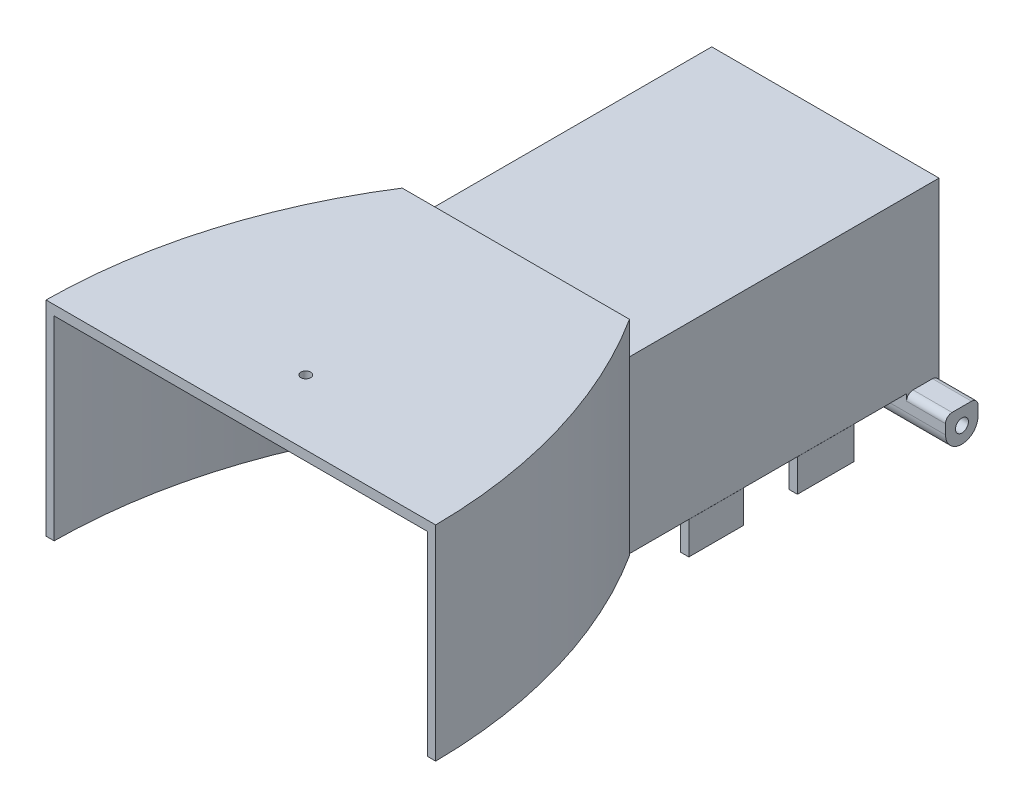
SolidWorks part; units mm, degrees
ref_plane "정면" through (0, 0, 0) normal (0, 0, 1) x (1, 0, 0)
ref_plane "윗면" through (0, 0, 0) normal (0, 1, 0) x (1, 0, 0)
ref_plane "우측면" through (0, 0, 0) normal (1, 0, 0) x (0, 0, -1)
sketch "스케치1" plane through (0, 0, 0) normal (0, 0, 1) x (1, 0, 0)
  line L1 (0, 0) -> (70, 0)
  line L2 (0, 0) -> (0, -70)
  line L3 (0, -70) -> (70, -70)
  line L4 (70, 0) -> (70, -70)
  dimension "D1" = 70
  dimension "D2" = 70
extrude "보스-돌출1" add sketch "스케치1" along normal blind 180 contours L1 L4 L3 L2
sketch "스케치3" plane through (0, 0, 180) normal (0, 0, 1) x (1, 0, 0)
  line L0 (0, 0) -> (70, 0) construction
  line L1 (2.5, -2.5) -> (67.5, -2.5)
  line L2 (2.5, -2.5) -> (2.5, -67.5)
  line L3 (2.5, -67.5) -> (67.5, -67.5)
  line L4 (67.5, -2.5) -> (67.5, -67.5)
  line L5 (70, 0) -> (70, -70) construction
  dimension "D1" = 65
  dimension "D2" = 65
  dimension "D3" = 2.5
  dimension "D4" = 2.5
extrude "컷-돌출1" cut sketch "스케치3" against normal blind 173 contours L1 L4 L3 L2
sketch "스케치4" plane through (0, 0, 0) normal (0, 0, -1) x (-1, 0, 0)
  line L0 (-35, 0) -> (-35, -51.7734)
  line L1 (0, 0) -> (-70, 0) construction
  line L2 (0, -70) -> (-70, -70) construction
  circle A0 centre (-35, -35) radius 10.95
  dimension "D1" = 21.9
  dimension "D2" = 35
extrude "컷-돌출2" cut sketch "스케치4" against normal blind 137 contours A0
sketch "스케치5" plane through (70, 0, 0) normal (1, 0, 0) x (0, 0, -1)
  line L0 (-180, 0) -> (-180, -70) construction
  line L1 (-180, -7.5) -> (-130, -7.5)
  line L2 (-180, -7.5) -> (-180, -62.5)
  line L3 (-180, -62.5) -> (-130, -62.5)
  line L4 (-130, -7.5) -> (-130, -62.5)
  line L5 (-180, 0) -> (0, 0) construction
  line L7 (-180, -70) -> (0, -70) construction
  dimension "D1" = 7.5
  dimension "D2" = 7.5
  dimension "D3" = 50
extrude "컷-돌출3" cut sketch "스케치5" against normal blind 137 contours L1 L4 L3 L2
sketch "스케치6" plane through (0, 0, 0) normal (-1, 0, 0) x (0, 0, 1)
  line L2 (180, 0) -> (0, 0) construction
  line L3 (20, -20) -> (55, -20)
  line L4 (20, -20) -> (20, -30)
  line L5 (20, -30) -> (55, -30)
  line L6 (55, -20) -> (55, -30)
  line L7 (180, -70) -> (0, -70) construction
  line L8 (20, -40) -> (55, -40)
  line L9 (20, -40) -> (20, -50)
  line L10 (20, -50) -> (55, -50)
  line L11 (55, -40) -> (55, -50)
  dimension "D2" = 35
  dimension "D3" = 20
  dimension "D4" = 10
  dimension "D5" = 35
  dimension "D6" = 10
  dimension "D7" = 20
extrude "보스-돌출2" add sketch "스케치6" against normal blind 18
ref_plane "평면5" through (35, 0, 0) normal (1, 0, 0) x (0, 0, -1)
mirror "대칭 복사1" about plane through (35, 0, 0) normal (1, 0, 0) of "보스-돌출2"
sketch "스케치7" plane through (0, 0, 7) normal (0, 0, 1) x (1, 0, 0)
  line L2 (70, -50) -> (0, -50)
  line L3 (70, -50) -> (70, -70)
  line L4 (70, -70) -> (0, -70)
  line L5 (0, -50) -> (0, -70)
  dimension "D1" = 70
extrude "컷-돌출4" cut sketch "스케치7" against normal through all both and the other way through all contours L2 L5 L4 L3
sketch "스케치9" plane through (0, -50, 0) normal (0, -1, 0) x (1, 0, 0)
  line L1 (0, 0) -> (70, 0)
  line L2 (0, 0) -> (0, 180)
  line L3 (0, 180) -> (70, 180)
  line L4 (70, 0) -> (70, 180)
extrude "보스-돌출3" add sketch "스케치9" along normal blind 2.5
sketch "스케치11" plane through (0, 0, 0) normal (0, 1, 0) x (1, 0, 0)
  line L0 (-25, -180) -> (95, -180)
  line L1 (0, -180) -> (0, 0) construction
  line L2 (0, -95.3205) -> (70, -95.3205)
  line L3 (70, -180) -> (70, 0) construction
  line L19 (70, -180) -> (95, -180)
  line L28 (-25, -180) -> (95, -180)
  arc A5 (-25, -180) -> (0, -95.3205) centre (134.9955, -181.2054) cw
  arc A6 (70, -95.3205) -> (95, -180) centre (-64.9955, -181.2054) cw
  dimension "D4" = 160
  dimension "D5" = 160
  dimension "D2" = 120
  dimension "D3" = 25
extrude "보스-돌출4" add sketch "스케치11" against normal blind 53 and the other way blind 10 contours L28 A5 L2 A6
sketch "스케치13" plane through (0, -53, 0) normal (0, -1, 0) x (1, 0, 0)
  line L1 (-25, 180) -> (95, 180) construction
  line L4 (-22.5, 180) -> (92.5, 180)
  line L5 (0.9416, 97.8205) -> (69.0584, 97.8205)
  arc A2 (0.9416, 97.8205) -> (-22.5, 180) centre (137.4955, 181.2054) cw
  arc A3 (92.5, 180) -> (69.0584, 97.8205) centre (-67.4955, 181.2054) cw
  dimension "D6" = 160
  dimension "D7" = 2.5
  dimension "D4" = 160
  dimension "D5" = 2.5
extrude "컷-돌출7" cut sketch "스케치13" against normal blind 60
sketch "스케치18" plane through (0, 0, 95.3205) normal (0, 0, -1) x (-1, 0, 0)
  line L0 (-70, 0) -> (0, 0) construction
  line L1 (-67.5, -2.5) -> (-2.5, -2.5)
  line L2 (-67.5, -2.5) -> (-67.5, -50)
  line L3 (-67.5, -50) -> (-2.5, -50)
  line L4 (-2.5, -2.5) -> (-2.5, -50)
  line L5 (-70, 0) -> (-70, -52.5) construction
  line L6 (0, 0) -> (0, -52.5) construction
  line L10 (0, -52.5) -> (-70, -52.5) construction
  dimension "D1" = 2.5
  dimension "D2" = 2.5
  dimension "D3" = 2.5
  dimension "D4" = 2.5
extrude "컷-돌출12" cut sketch "스케치18" against normal blind 105 contours L1 L4 L3 L2
sketch "스케치20" plane through (0, -52.5, 0) normal (0, -1, 0) x (1, 0, 0)
  line L0 (0, 95.3205) -> (0, 0) construction
  line L1 (2.5, 7) -> (67.5, 7)
  line L2 (2.5, 7) -> (2.5, 132.5186)
  line L3 (2.5, 132.5186) -> (67.5, 132.5186)
  line L4 (67.5, 7) -> (67.5, 132.5186)
  line L5 (0, 0) -> (70, 0) construction
  line L6 (70, 0) -> (70, 95.3205) construction
  dimension "D1" = 2.5
  dimension "D2" = 7
  dimension "D3" = 2.5
extrude "컷-돌출13" cut sketch "스케치20" against normal blind 2.5 and the other way blind 105
sketch "스케치21" plane through (0, 10, 0) normal (0, 1, 0) x (1, 0, 0)
  line L1 (-25, -180) -> (-25, -84.6336)
  line L2 (35, -180) -> (35, -50.371)
  line L3 (-25, -180) -> (95, -180) construction
  line L4 (35, -27.775) -> (35, 27.775) construction
  line L5 (-36.5752, -160) -> (130.3519, -160)
  circle A1 centre (35, -160) radius 1.5
  dimension "D3" = 3
  dimension "D1" = 120
  dimension "D2" = 20
extrude "컷-돌출14" cut sketch "스케치21" against normal blind 10 contours A1
sketch "스케치23" plane through (0, -52.5, 0) normal (0, -1, 0) x (1, 0, 0)
  line L1 (0, 95.3205) -> (0, 0) construction
  line L2 (-12, 10) -> (82, 10)
  line L3 (-12, 10) -> (-12, 0)
  line L4 (-12, 0) -> (82, 0)
  line L5 (82, 10) -> (82, 0)
  dimension "D1" = 10
  dimension "D2" = 94
  dimension "D3" = 12
extrude "보스-돌출5" add sketch "스케치23" along normal blind 10
sketch "스케치24" plane through (-12, 0, 0) normal (-1, 0, 0) x (0, 0, 1)
  line L0 (10, -62.5) -> (10, -52.5) construction
  line L1 (10, -62.5) -> (0, -62.5) construction
  circle A0 centre (4.9374, -57.5) radius 2
  dimension "D1" = 4
  dimension "D2" = 5.0626
  dimension "D3" = 5
extrude "컷-돌출15" cut sketch "스케치24" against normal blind 194
fillet "필렛1" radius 2 1 edges at (35, -52.5, 10)
fillet "필렛2" radius 2 2 edges at (76, -52.5, 10) (-6, -52.5, 10)
fillet "필렛3" radius 2 2 edges at (-6, -52.5, 0) (76, -52.5, 0)
fillet "필렛4" radius 5 2 edges at (35, -62.5, 10) (35, -62.5, 0)
sketch "스케치25" plane through (0, -52.5, 0) normal (0, -1, 0) x (1, 0, 0)
  line L0 (67.5, 77.0704) -> (67.5, 60.2849)
  line L1 (67.5, 77.0704) -> (70.03, 77.0704)
  line L2 (67.5, 60.2849) -> (70.03, 60.2849)
  line L3 (70.03, 77.0704) -> (70.03, 60.2849)
  line L4 (67.5, 7) -> (67.5, 97.8205) construction
  line L6 (67.5, 43.6405) -> (67.5, 26.1498)
  line L7 (67.5, 43.6405) -> (70.03, 43.6405)
  line L8 (67.5, 26.1498) -> (70.03, 26.1498)
  line L9 (70.03, 43.6405) -> (70.03, 26.1498)
  line L10 (67.5, 20) -> (67.5, 55) construction
  line L12 (2.5, 77.0704) -> (0, 77.0704)
  line L13 (2.5, 77.0704) -> (2.5, 60.2849)
  line L14 (0, 77.0704) -> (0, 60.2849)
  line L15 (2.5, 60.2849) -> (0, 60.2849)
  line L18 (2.5, 7) -> (2.5, 97.8205) construction
  line L19 (0, 95.3205) -> (0, 10) construction
  line L20 (2.5, 43.6405) -> (0, 43.6405)
  line L21 (2.5, 43.6405) -> (2.5, 26.2908)
  line L22 (0, 43.6405) -> (0, 26.2908)
  line L23 (2.5, 26.2908) -> (0, 26.2908)
  line L25 (2.5, 95.3205) -> (2.5, 10) construction
extrude "보스-돌출6" add sketch "스케치25" along normal blind 10
